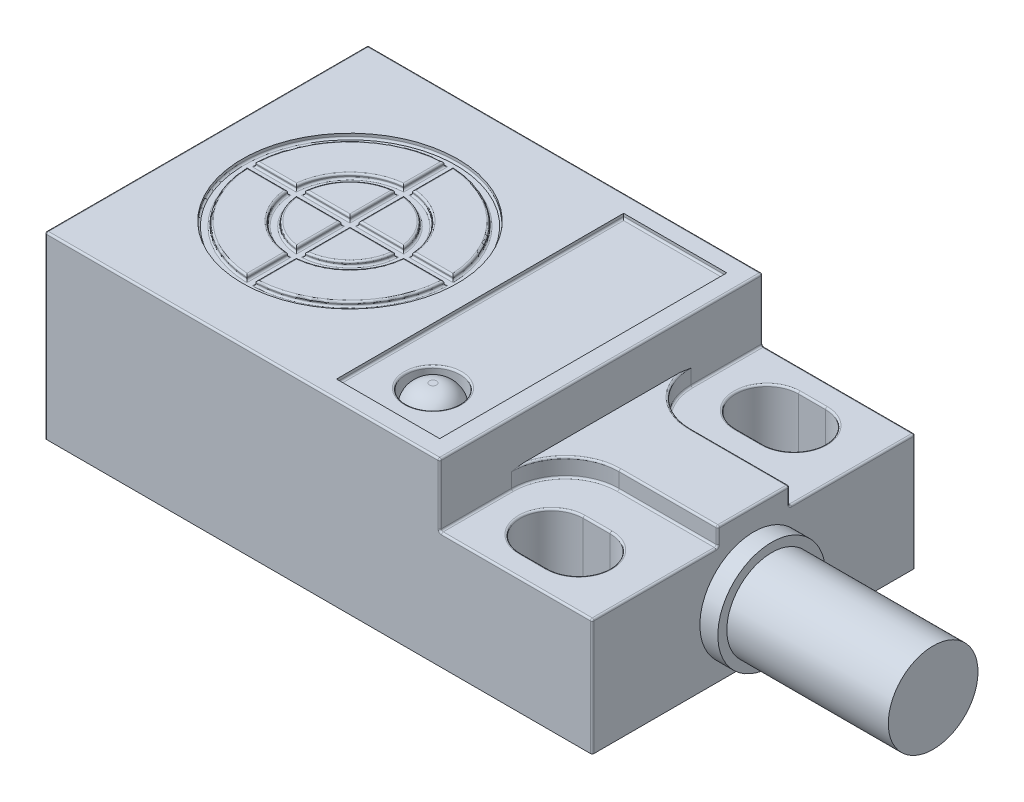
SolidWorks part; units mm, degrees
ref_plane "Front Plane" through (0, 0, 0) normal (0, 0, 1) x (1, 0, 0)
ref_plane "Top Plane" through (0, 0, 0) normal (0, 1, 0) x (1, 0, 0)
ref_plane "Right Plane" through (0, 0, 0) normal (1, 0, 0) x (0, 0, -1)
sketch "Sketch1" plane through (0, 0, 0) normal (0, 1, 0) x (1, 0, 0)
  line L4 (17.25, 6) -> (18.75, 6) construction
  line L5 (-8, 9) -> (22.5, 9)
  line L6 (-8, 9) -> (-8, -9)
  line L7 (-8, -9) -> (22.5, -9)
  line L8 (22.5, 9) -> (22.5, -9)
  line L9 (7.25, -9) -> (7.25, 9) construction
  line L10 (-8, 0) -> (22.5, 0) construction
  line L11 (17.25, 7.75) -> (18.75, 7.75)
  line L12 (17.25, 4.25) -> (18.75, 4.25)
  line L13 (17.25, -6) -> (18.75, -6) construction
  line L14 (17.25, -7.75) -> (18.75, -7.75)
  line L15 (17.25, -4.25) -> (18.75, -4.25)
  line L16 (22.5, 2) -> (17, 2)
  line L17 (14, 5) -> (14, 9)
  line L18 (14, -5) -> (14, -9)
  line L19 (22.5, -2) -> (17, -2)
  line L20 (14, 5) -> (14, -5)
  circle A1 centre (0, 0) radius 6 construction
  arc A2 (17.25, 7.75) -> (17.25, 4.25) centre (17.25, 6) ccw
  arc A3 (18.75, 4.25) -> (18.75, 7.75) centre (18.75, 6) ccw
  arc A4 (17.25, -7.75) -> (17.25, -4.25) centre (17.25, -6) cw
  arc A5 (18.75, -4.25) -> (18.75, -7.75) centre (18.75, -6) cw
  arc A6 (17, 2) -> (14, 5) centre (17, 5) cw
  arc A7 (17, -2) -> (14, -5) centre (17, -5) ccw
  point P7 (18, 6)
  point P17 (20.5, 6)
  point P18 (15.5, 6)
  point P21 (18, -6)
  point P148 (7.25, 0)
  dimension "D1" = 18
  dimension "D2" = 12
  dimension "D5" = 3.5
  dimension "D11" = 3
  dimension "D3" = 30.5
  dimension "D4" = 5
  dimension "D6" = 4.5
  dimension "D7" = 18
  dimension "D8" = 12
  dimension "D9" = 2
  dimension "D10" = 8.5
extrude "Boss-Extrude1" add sketch "Sketch1" along normal blind 10 contours L20 L17 L5 L6 L7 L18 region at (3, 0, 0)
extrude "Boss-Extrude2" add sketch "Sketch1<3>" along normal blind 6.5 contours L19 A7 L18 L7 L8 L15 A5 L14 A4 | A6 L16 L8 L5 L17 A3 L12 A2 L11 region at (18.25, 0, -8.8899) region at (14.1101, 0, 7)
sketch "Sketch1<3>" plane through (0, 0, 0) normal (0, 1, 0) x (1, 0, 0) same geometry as "Sketch1"
extrude "Boss-Extrude3" add sketch "Sketch1<4>" along normal blind 7.5 contours A7 L19 L8 L16 A6 L20 region at (17.8848, 0, 0)
sketch "Sketch1<4>" plane through (0, 0, 0) normal (0, 1, 0) x (1, 0, 0) same geometry as "Sketch1"
sketch "Sketch2" plane through (22.5, 0, 0) normal (1, 0, 0) x (0, 0, -1)
  line L0 (0, 0) -> (0, 6.5) construction
  line L1 (-2, 6.5) -> (-9, 6.5) construction
  circle A0 centre (0, 3.25) radius 3
  circle A1 centre (0, 3.25) radius 2.5
  dimension "D1" = 6
  dimension "D2" = 5
extrude "Boss-Extrude4" add sketch "Sketch2" along normal blind 1
extrude "Boss-Extrude5" add sketch "Sketch2<3>" along normal blind 10 contours L0 A1 | A1 L0 region at (22.5, 3.25, 1.061) region at (22.5, 3.25, -1.061)
sketch "Sketch2<3>" plane through (22.5, 0, 0) normal (1, 0, 0) x (0, 0, -1) same geometry as "Sketch2"
sketch "Sketch3" plane through (0, 10, 0) normal (0, 1, 0) x (1, 0, 0)
  line L0 (14, 5) -> (14, 9) construction
  line L1 (13, 8) -> (7.25, 8)
  line L2 (13, 8) -> (13, -8)
  line L3 (13, -8) -> (7.25, -8)
  line L4 (7.25, 8) -> (7.25, -8)
  line L5 (10.125, -8) -> (10.125, 8) construction
  line L6 (13, 0) -> (7.25, 0) construction
  line L7 (-8, 9) -> (22.5, 9) construction
  line L8 (7.25, -9) -> (7.25, 9) construction
  line L9 (0, 6) -> (0, -6) construction
  line L10 (-6, 0) -> (6, 0) construction
  line L11 (-0.25, 6) -> (-0.25, -6)
  line L12 (0.25, 6) -> (0.25, -6)
  line L13 (-6, -0.25) -> (6, -0.25)
  line L14 (-6, 0.25) -> (6, 0.25)
  circle A0 centre (10.125, -5.5) radius 1.5
  circle A1 centre (0, 0) radius 6 construction
  circle A2 centre (0, 0) radius 6
  circle A3 centre (0, 0) radius 5.5
  circle A4 centre (0, 0) radius 3.25
  circle A5 centre (0, 0) radius 2.75
  point P208 (10.125, 0)
  dimension "D3" = 3
  dimension "D4" = 5.5
  dimension "D6" = 6.5
  dimension "D1" = 1
  dimension "D2" = 1
  dimension "D8" = 0.25
  dimension "D5" = 0.5
  dimension "D7" = 0.5
  dimension "D9" = 0.25
  dimension "D10" = 0.25
  dimension "D11" = 0.25
extrude "Cut-Extrude2" cut sketch "Sketch3" against normal blind 0.25 contours L2 L3 L4 L1
extrude "Cut-Extrude3" cut sketch "Sketch3<5>" against normal blind 0.25 contours A2 | A3 | A4 | A5
sketch "Sketch3<5>" plane through (0, 10, 0) normal (0, 1, 0) x (1, 0, 0) same geometry as "Sketch3"
extrude "Cut-Extrude4" cut sketch "Sketch3<6>" against normal blind 0.25 contours A4 L12 A3 L11 | L12 A5 L11 L14 | L11 A5 L12 L13 | A4 L11 A3 L12 | A4 L13 A3 L14 | L13 A5 L14 L12 | L14 L11 L13 L12 | L14 A5 L13 L11 | A4 L14 A3 L13 region at (0, 10, -4.3724) region at (-4.3724, 10, 0) region at (0, 10, -1.4981) region at (4.3724, 10, 0) region at (0, 10, 0) region at (-1.4981, 10, 0) region at (0, 10, 4.3724) region at (0, 10, 1.4981) region at (1.4981, 10, 0)
sketch "Sketch3<6>" plane through (0, 10, 0) normal (0, 1, 0) x (1, 0, 0) same geometry as "Sketch3"
extrude "Cut-Extrude5" cut sketch "Sketch3<7>" against normal blind 3 contours A0 region at (10.125, 10, 5.5)
sketch "Sketch3<7>" plane through (0, 10, 0) normal (0, 1, 0) x (1, 0, 0) same geometry as "Sketch3"
fillet "Fillet1" radius 0.1 97 edges at (22.5, 7, -2) (22.5, 7, 2) (14, 8.25, -9) (14, 8.25, 9) (19.75, 6.5, -2) (14.8787, 6.5, -2.8787) (19.75, 6.5, 2) (14.8787, 6.5, 2.8787) (18, 6.5, 4.25) (15.5, 6.5, 6) (18, 6.5, 7.75) (18, 6.5, -4.25) (15.5, 6.5, -6) (18, 6.5, -7.75) (19.75, 7.5, 2) (19.75, 7.5, -2) (3, 10, 9) (-8, 10, 0) (3, 10, -9) (14, 10, 0) (0, 9.75, 6) (0.25, 9.75, 4.3673) (3.8891, 9.75, 3.8891) (4.3673, 9.75, 0.25) (2.2981, 9.75, 2.2981) (1.4943, 9.75, 0.25) (0.25, 9.75, 1.4943) (1.9445, 9.75, 1.9445) (0.25, 9.75, -1.4943) (1.4943, 9.75, -0.25) (1.9445, 9.75, -1.9445) (-1.4943, 9.75, -0.25) (-0.25, 9.75, -1.4943) (-1.9445, 9.75, -1.9445) (-0.25, 9.75, 1.4943) (-1.4943, 9.75, 0.25) (-1.9445, 9.75, 1.9445) (0.25, 9.75, -4.3673) (2.2981, 9.75, -2.2981) (4.3673, 9.75, -0.25) (3.8891, 9.75, -3.8891) (-0.25, 9.75, 4.3673) (-2.2981, 9.75, 2.2981) (-4.3673, 9.75, 0.25) (-3.8891, 9.75, 3.8891) (-4.3673, 9.75, -0.25) (-2.2981, 9.75, -2.2981) (-0.25, 9.75, -4.3673) (-3.8891, 9.75, -3.8891) (13, 9.75, 0) (10.125, 9.75, 8) (7.25, 9.75, 0) (10.125, 9.75, -8) (10.125, 9.75, 7) (3.8891, 10, 3.8891) (0.25, 10, 4.3673) (2.2981, 10, 2.2981) (4.3673, 10, 0.25) (1.9445, 10, 1.9445) (0.25, 10, 1.4943) (1.4943, 10, 0.25) (1.4943, 10, -0.25) (0.25, 10, -1.4943) (1.9445, 10, -1.9445) (-1.9445, 10, 1.9445) (-1.4943, 10, 0.25) (-0.25, 10, 1.4943) (-0.25, 10, -1.4943) (-1.4943, 10, -0.25) (-1.9445, 10, -1.9445) (-2.2981, 10, 2.2981) (-0.25, 10, 4.3673) (-3.8891, 10, 3.8891) (-4.3673, 10, 0.25) (-2.2981, 10, -2.2981) (-4.3673, 10, -0.25) (-3.8891, 10, -3.8891) (-0.25, 10, -4.3673) (4.3673, 10, -0.25) (2.2981, 10, -2.2981) (0.25, 10, -4.3673) (3.8891, 10, -3.8891) (-8, 5, -9) (22.5, 7.5, 0) (14, 6.5, -7) (14, 6.5, 7) (18.25, 6.5, 9) (22.5, 6.5, 5.5) (20.5, 6.5, 6) (20.5, 6.5, -6) (22.5, 6.5, -5.5) (18.25, 6.5, -9) (22.5, 3.25, -9) (22.5, 3.25, 9) (-8, 5, 9) (14.8787, 7.5, 2.8787) (14.8787, 7.5, -2.8787)
sketch "Sketch4" plane through (0, 7, 0) normal (0, 1, 0) x (1, 0, 0)
  circle A4 centre (10.125, -5.5) radius 1.4
  circle A6 centre (10.125, -5.5) radius 1.4
  dimension "D1" = 0.1
extrude "Boss-Extrude6" add sketch "Sketch4" along normal blind 3
fillet "Fillet2" radius 1.2 1 edges at (10.125, 10, 6.9)
